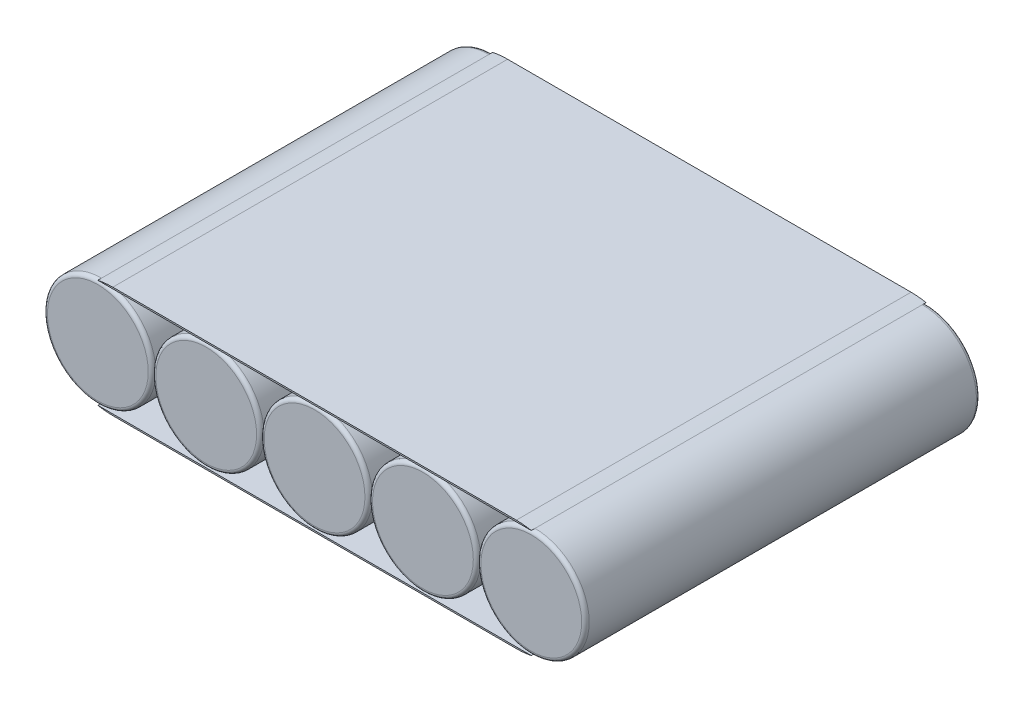
SolidWorks part; units mm, degrees
ref_plane "Front Plane" through (0, 0, 0) normal (0, 0, 1) x (1, 0, 0)
ref_plane "Top Plane" through (0, 0, 0) normal (0, 1, 0) x (1, 0, 0)
ref_plane "Right Plane" through (0, 0, 0) normal (1, 0, 0) x (0, 0, -1)
sketch "Sketch1" plane through (0, 0, 0) normal (0, 0, 1) x (1, 0, 0)
  circle A0 centre (0, 0) radius 7.2
  circle A1 centre (-14.41, 0) radius 7.2
  circle A2 centre (-28.82, 0) radius 7.2
  circle A3 centre (14.41, 0) radius 7.2
  circle A4 centre (28.82, 0) radius 7.2
  point P11 (-16.0798, 0)
  dimension "D1" = 14.4
  dimension "D2" = 14.4
  dimension "D3" = 14.4
  dimension "D4" = 14.4
  dimension "D5" = 14.4
  dimension "D6" = 14.41
  dimension "D7" = 14.41
  dimension "D8" = 14.41
  dimension "D9" = 14.41
extrude "Boss-Extrude1" add sketch "Sketch1" along normal blind 52.5
ref_plane "Plane1" through (0, 7.2, 0) normal (0, 1, 0) x (1, 0, 0)
sketch "Sketch3" plane through (0, 7.2, 0) normal (0, 1, 0) x (1, 0, 0)
  line L0 (21.62, -52.5) -> (36.02, -52.5) construction
  line L1 (-28.82, 0) -> (28.82, 0)
  line L2 (-28.82, 0) -> (-28.82, -52.5)
  line L3 (-28.82, -52.5) -> (28.82, -52.5)
  line L4 (28.82, 0) -> (28.82, -52.5)
  line L5 (36.02, 0) -> (21.62, 0) construction
  line L7 (36.02, -52.5) -> (36.02, 0) construction
  line L8 (-36.02, 0) -> (-36.02, -52.5) construction
  dimension "D1" = 0
  dimension "D2" = 0
  dimension "D3" = 7.2
  dimension "D4" = 7.2
extrude "Boss-Extrude2" add sketch "Sketch3" along normal blind 0.2 separate body
ref_plane "Plane2" through (0, -7.2, 0) normal (0, -1, 0) x (-1, 0, 0)
sketch "Sketch5" plane through (0, -7.2, 0) normal (0, -1, 0) x (-1, 0, 0)
  line L0 (-36.02, 0) -> (-36.02, -52.5) construction
  line L1 (28.82, -52.5) -> (-28.82, -52.5)
  line L2 (28.82, -52.5) -> (28.82, 0)
  line L3 (28.82, 0) -> (-28.82, 0)
  line L4 (-28.82, -52.5) -> (-28.82, 0)
  line L5 (7.21, -52.5) -> (21.61, -52.5) construction
  line L6 (21.61, 0) -> (7.21, 0) construction
  line L7 (36.02, -52.5) -> (36.02, 0) construction
  dimension "D1" = 7.2
  dimension "D2" = 0
  dimension "D3" = 0
  dimension "D4" = 7.2
extrude "Boss-Extrude3" add sketch "Sketch5" along normal blind 0.2 separate body
fillet "Fillet2" radius 10 2 edges at (-28.82, 7.4, 26.25) (28.82, 7.4, 26.25)
fillet "Fillet3" radius 10 2 edges at (28.82, -7.4, 26.25) (-28.82, -7.4, 26.25)
fillet "Fillet4" radius 0.5 2 edges at (-21.62, 0, 0) (-21.62, 0, 52.5)
fillet "Fillet5" radius 0.5 2 edges at (-7.21, 0, 52.5) (-7.21, 0, 0)
fillet "Fillet6" radius 0.5 2 edges at (7.2, 0, 0) (7.2, 0, 52.5)
fillet "Fillet7" radius 0.5 2 edges at (21.61, 0, 0) (21.61, 0, 52.5)
fillet "Fillet8" radius 0.5 2 edges at (36.02, 0, 52.5) (36.02, 0, 0)
